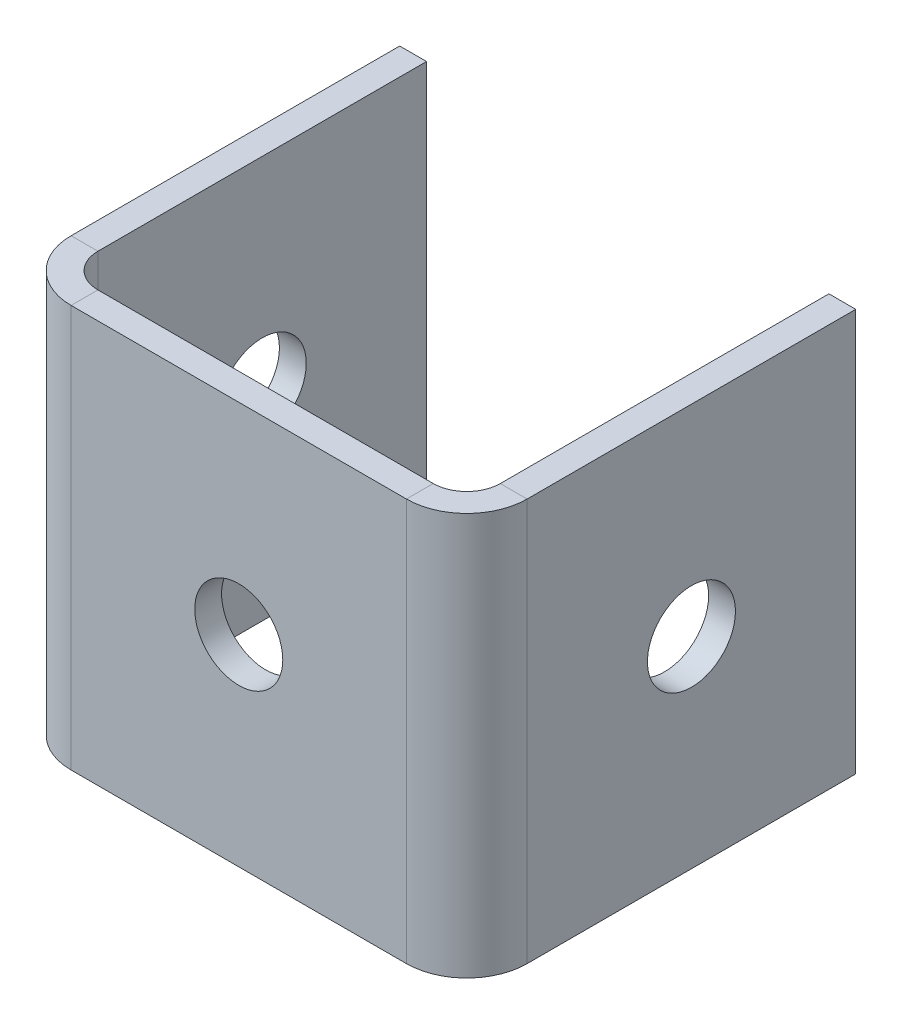
SolidWorks part; units mm, degrees
note: The reader was unsure of these and kept them because the rebuilt part matched: flange length of "Edge-Flange2".
ref_plane "Front Plane" through (0, 0, 0) normal (0, 0, 1) x (1, 0, 0)
ref_plane "Top Plane" through (0, 0, 0) normal (0, 1, 0) x (1, 0, 0)
ref_plane "Right Plane" through (0, 0, 0) normal (1, 0, 0) x (0, 0, -1)
sketch "Sketch2" plane through (0, 0, 0) normal (0, 0, 1) x (1, 0, 0)
  line L1 (-15.875, 19.05) -> (15.875, 19.05)
  line L2 (-15.875, 19.05) -> (-15.875, -19.05)
  line L3 (-15.875, -19.05) -> (15.875, -19.05)
  line L4 (15.875, 19.05) -> (15.875, -19.05)
  line L5 (-15.875, 19.05) -> (15.875, -19.05) construction
  line L6 (-15.875, -19.05) -> (15.875, 19.05) construction
  point P0 (0, 0)
  dimension "D1" = 31.75
  dimension "D2" = 38.1
base flange "Base-Flange1" sketch "Sketch2" thickness 2.54 reverse thickness direction no parameters "D1"=6.35
edge flange "Edge-Flange2" sketch "Sketch20" flange profiles "Sketch20", "Sketch21" flange angle 90 flange length 34.29 flange position bend outside bend radius 3.175 thickness 2.54 relief rectangular parameters "D6"=10, "D8"=0.254
sketch "Sketch20" plane through (15.875, 0, -2.54) normal (1, 0, 0) x (0, -1, 0)
  line L2 (-19.05, 0) -> (-19.05, 34.29)
  line L3 (-19.05, 34.29) -> (19.05, 34.29)
  line L4 (19.05, 34.29) -> (19.05, 0)
  line L11 (19.05, 0) -> (-19.05, 0) construction
  line L12 (19.05, 0) -> (-19.05, 0)
sketch "Sketch21" plane through (-15.875, 0, -2.54) normal (-1, 0, 0) x (0, 1, 0)
  line L0 (19.05, 0) -> (-19.05, 0) construction
  line L1 (19.05, 0) -> (-19.05, 0)
  line L2 (-19.05, 0) -> (-19.05, 34.29)
  line L3 (-19.05, 34.29) -> (19.05, 34.29)
  line L4 (19.05, 34.29) -> (19.05, 0)
bend "EdgeBend2" bend radius 3.175 bend angle 90 parameters "D5"=1
bend "EdgeBend3" bend radius 3.175 bend angle 90 parameters "D5"=2
hole_wizard "21/64 (0.32813) Diameter Hole1" positions "Sketch22" profile "Sketch23" hole size "21/64" standard "ANSI Inch"
sketch "Sketch22" plane through (0, 0, 0) normal (0, 0, 1) x (1, 0, 0)
  point P0 (0, 0)
sketch "Sketch23" plane through (0, 0, 0) normal (1, 0, 0) x (0, -1, 0)
  line L0 (0, 0) -> (0, 27.9039)
  line L1 (0, 27.9039) -> (4.1673, 25.4)
  line L2 (4.1673, 25.4) -> (4.1673, 0)
  line L5 (4.1673, 0) -> (0, 0)
  line L10 (0, 27.9039) -> (-4.1673, 25.4) construction
  line L11 (0, -6.35) -> (0, 107.95) construction
  dimension "Hole Dia." = 8.3345
  dimension "Hole Depth" = 25.4
  dimension "Drill Angle" = 118
hole_wizard "21/64 (0.32813) Diameter Hole2" positions "Sketch24" profile "Sketch26" hole size "21/64" standard "ANSI Inch" end condition through all
sketch "Sketch24" plane through (21.59, 0, 0) normal (1, 0, 0) x (0, 0, -1)
  line L0 (5.715, -19.05) -> (36.83, -19.05) construction
  line L1 (36.83, -19.05) -> (36.83, 19.05) construction
  point P0 (21.2725, 0)
  point P12 (-73.9137, 33.2698)
  dimension "D1" = 19.05
  dimension "D2" = 15.5575
sketch "Sketch26" plane through (21.59, 0, -21.2725) normal (0, 1, 0) x (0, 0, -1)
  line L0 (0, 0) -> (0, 43.18)
  line L1 (0, 43.18) -> (4.1673, 43.18)
  line L2 (4.1673, 43.18) -> (4.1673, 0)
  line L5 (4.1673, 0) -> (0, 0)
  line L11 (0, -6.35) -> (0, 107.95) construction
  dimension "Thru Hole Dia." = 8.3345
  dimension "Thru Hole Depth" = 43.18
sketch "Bend-Lines1" [suppressed] plane through (0, 0, 0) normal (0, 1, 0) x (1, 0, 0)
sketch "Bounding-Box1" [suppressed] plane through (0, 0, 0) normal (0, 1, 0) x (1, 0, 0)
sheet metal parameters "Sheet-Metal1" thickness 2.54 parameters "D1"=0.7366
flat pattern "Flat-Pattern1" [suppressed]
sketch "Bend-Lines2" plane through (0, 0, 0) normal (0, 1, 0) x (1, 0, 0)
sketch3d "Bounding-Box2" [suppressed]
  line L0 (-19.05, -19.05, 0) -> (19.05, -19.05, 0) construction
  line L1 (-19.05, 19.05, 0) -> (19.05, 19.05, 0) construction
  line L2 (-19.05, -19.05, 0) -> (-19.05, 19.05, 0) construction
  line L3 (19.05, -19.05, 0) -> (19.05, 19.05, 0) construction
sheet metal parameters "Sheet-Metal3" thickness 2.54 parameters "D1"=0.7366
flat pattern "Flat-Pattern1"
sketch "Bend-Lines2" plane through (0, 0, 0) normal (0, 0, 1) x (1, 0, 0)
  line L0 (-17.78, 19.05) -> (-17.78, -19.05) construction
  line L1 (17.78, -19.05) -> (17.78, 19.05) construction
  line L2 (-17.78, 19.05) -> (-17.78, -19.05) construction
  line L3 (17.78, -19.05) -> (17.78, 19.05) construction
sketch3d "Bounding-Box2" [suppressed]
  line L0 (-41.91, -19.05, 0) -> (41.91, -19.05, 0) construction
  line L1 (-41.91, 19.05, 0) -> (41.91, 19.05, 0) construction
  line L2 (-41.91, -19.05, 0) -> (-41.91, 19.05, 0) construction
  line L3 (41.91, -19.05, 0) -> (41.91, 19.05, 0) construction
bend of the flat pattern "Flatten-<EdgeBend2>1"
bend of the flat pattern "Flatten-<EdgeBend3>1"
sheet metal parameters "Sheet-Metal4" thickness 2.54 parameters "D1"=0.7366
flat pattern "Flat-Pattern1"
sketch "Bend-Lines2" plane through (0, 0, 0) normal (0, 0, 1) x (1, 0, 0)
  line L0 (-17.78, 19.05) -> (-17.78, -19.05) construction
  line L1 (17.78, -19.05) -> (17.78, 19.05) construction
  line L2 (-17.78, 19.05) -> (-17.78, -19.05) construction
  line L3 (17.78, -19.05) -> (17.78, 19.05) construction
sketch3d "Bounding-Box2" [suppressed]
  line L0 (-41.91, -19.05, 0) -> (41.91, -19.05, 0) construction
  line L1 (-41.91, 19.05, 0) -> (41.91, 19.05, 0) construction
  line L2 (-41.91, -19.05, 0) -> (-41.91, 19.05, 0) construction
  line L3 (41.91, -19.05, 0) -> (41.91, 19.05, 0) construction
bend of the flat pattern "Flatten-<EdgeBend2>1"
bend of the flat pattern "Flatten-<EdgeBend3>1"
sheet metal parameters "Sheet-Metal5" thickness 2.54 parameters "D1"=0.7366
flat pattern "Flat-Pattern1"
sketch "Bend-Lines2" plane through (0, 0, 0) normal (0, 0, 1) x (1, 0, 0)
  line L0 (-17.78, 19.05) -> (-17.78, -19.05) construction
  line L1 (17.78, -19.05) -> (17.78, 19.05) construction
  line L2 (-17.78, 19.05) -> (-17.78, -19.05) construction
  line L3 (17.78, -19.05) -> (17.78, 19.05) construction
sketch3d "Bounding-Box2" [suppressed]
  line L0 (-41.91, -19.05, 0) -> (41.91, -19.05, 0) construction
  line L1 (-41.91, 19.05, 0) -> (41.91, 19.05, 0) construction
  line L2 (-41.91, -19.05, 0) -> (-41.91, 19.05, 0) construction
  line L3 (41.91, -19.05, 0) -> (41.91, 19.05, 0) construction
bend of the flat pattern "Flatten-<EdgeBend2>1"
bend of the flat pattern "Flatten-<EdgeBend3>1"
